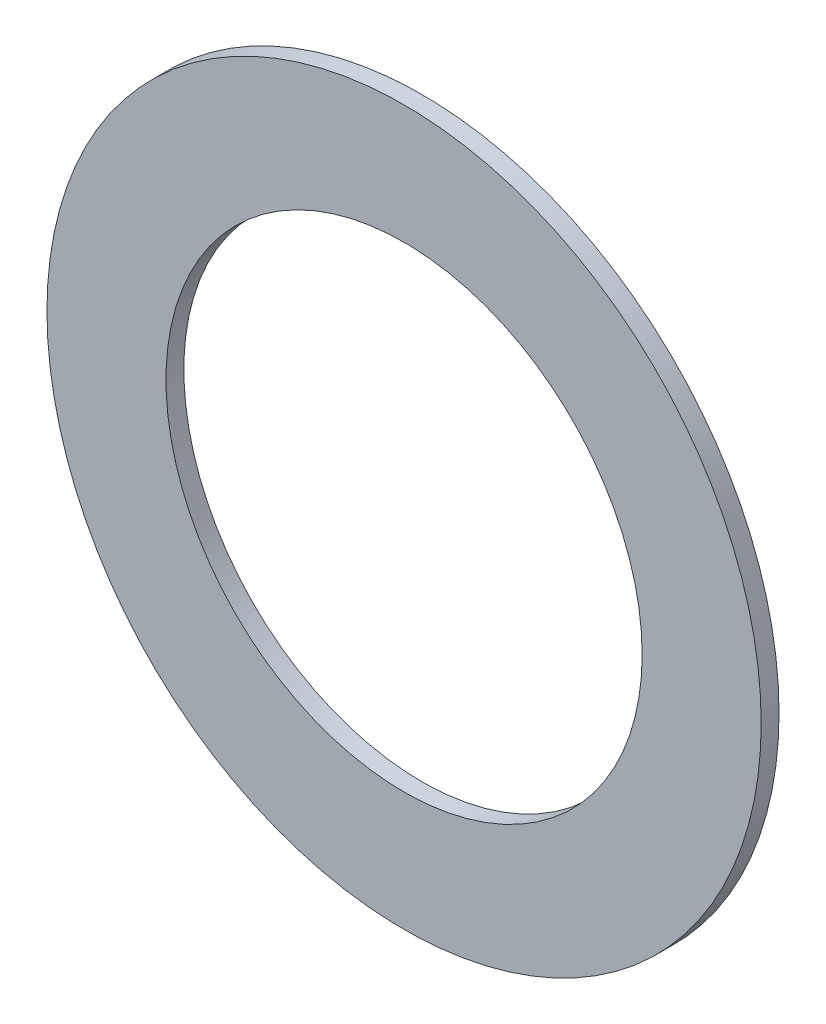
SolidWorks part; units mm, degrees
material "PA Type 6"
ref_plane "Front Plane" through (0, 0, 0) normal (0, 0, 1) x (1, 0, 0)
ref_plane "Top Plane" through (0, 0, 0) normal (0, 1, 0) x (1, 0, 0)
ref_plane "Right Plane" through (0, 0, 0) normal (1, 0, 0) x (0, 0, -1)
sketch "Sketch1" plane through (0, 0, 0) normal (0, 0, 1) x (1, 0, 0)
  circle A0 centre (0, 0) radius 20
  circle A1 centre (0, 0) radius 30
  dimension "D1" = 40
  dimension "D2" = 60
extrude "Boss-Extrude1" add sketch "Sketch1" along normal blind 1.5
